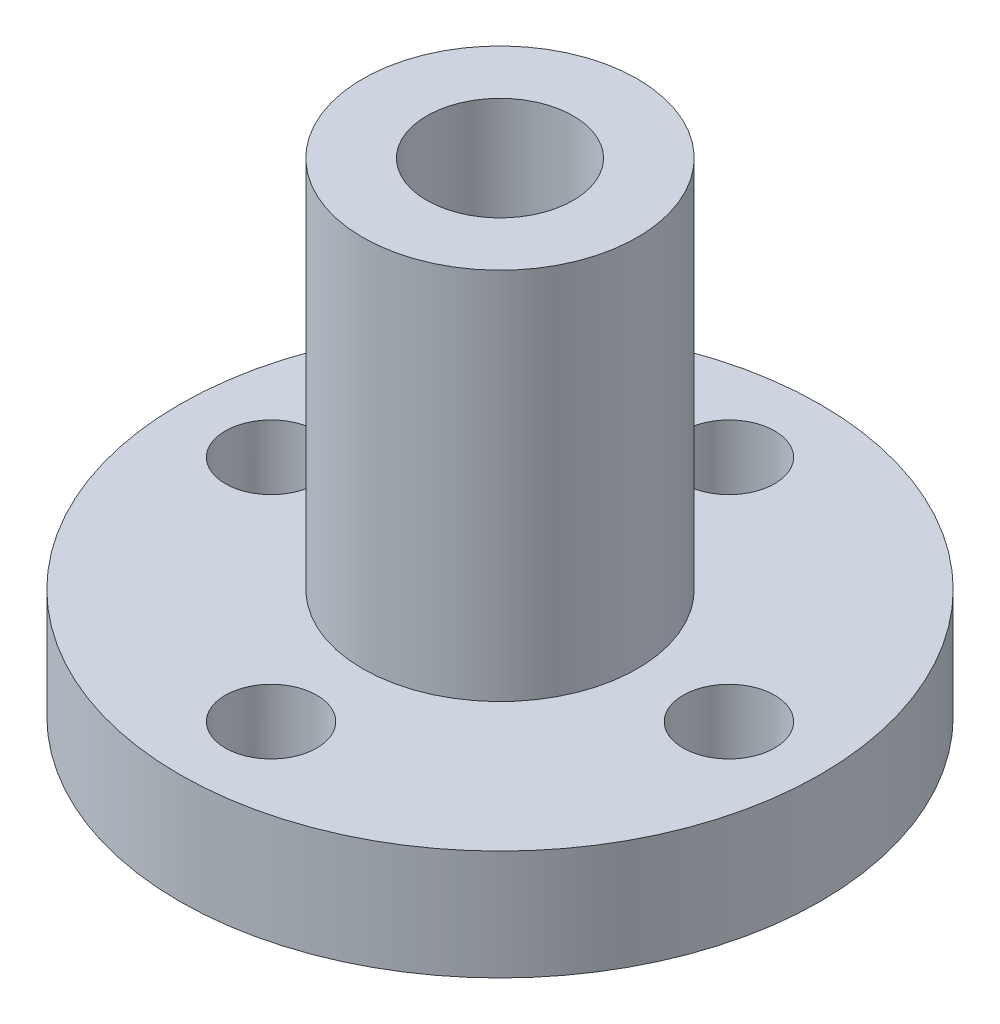
SolidWorks part; units mm, degrees
ref_plane "前视基准面" through (0, 0, 0) normal (0, 0, 1) x (1, 0, 0)
ref_plane "上视基准面" through (0, 0, 0) normal (0, 1, 0) x (1, 0, 0)
ref_plane "右视基准面" through (0, 0, 0) normal (1, 0, 0) x (0, 0, -1)
other "Configuration Table"
sketch "草图1" plane through (0, 0, 0) normal (0, 1, 0) x (1, 0, 0)
  circle A0 centre (0, 0) radius 17.5
  dimension "D1" = 35
extrude "凸台-拉伸1" add sketch "草图1" along normal blind 6
sketch "草图3" plane through (0, 6, 0) normal (0, 1, 0) x (1, 0, 0)
  circle A0 centre (0, 0) radius 7.5
  dimension "D1" = 15
extrude "凸台-拉伸2" add sketch "草图3" along normal blind 20.4
sketch "草图4" plane through (0, 26.4, 0) normal (0, 1, 0) x (1, 0, 0)
  circle A0 centre (0, 0) radius 4
  dimension "D1" = 8
extrude "切除-拉伸1" cut sketch "草图4" against normal through all
sketch "草图5" plane through (0, 6, 0) normal (0, 1, 0) x (1, 0, 0)
  circle A0 centre (0, 0) radius 12.5 construction
  circle A1 centre (0, 12.5) radius 2.5
  dimension "D1" = 25
  dimension "D2" = 5
extrude "切除-拉伸2" cut sketch "草图5" against normal blind 10
pattern_circular "阵列(圆周)1" count 4 every 90 about axis through (0, 6, 0) along (0, 1, 0) of "切除-拉伸2"
